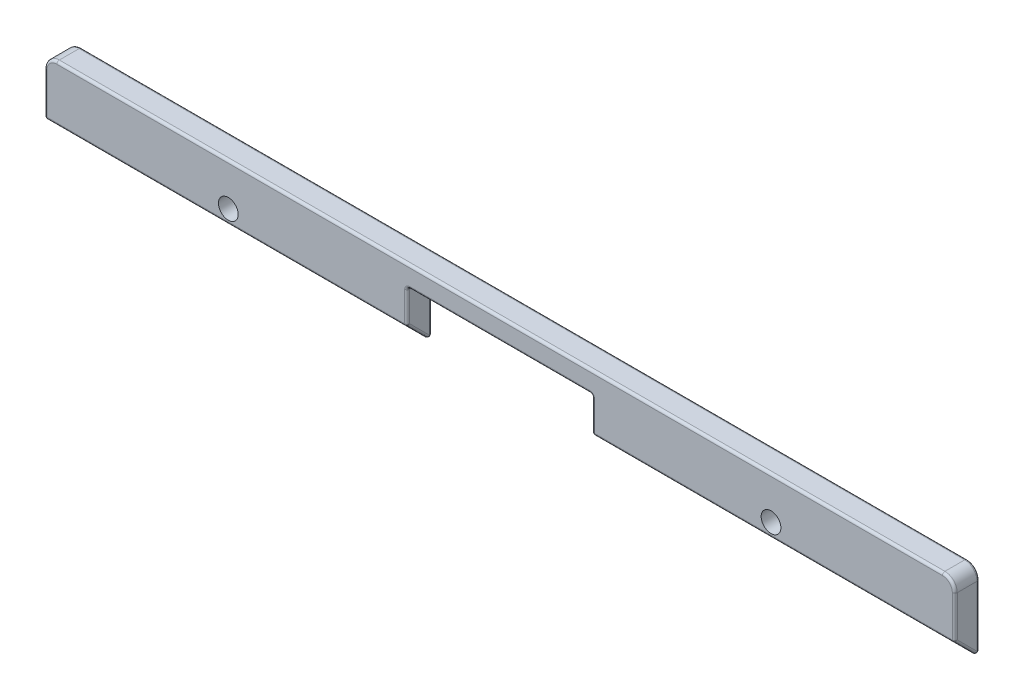
SolidWorks part; units mm, degrees
material "6061-T6 (SS)"
ref_plane "Front Plane" through (0, 0, 0) normal (0, 0, 1) x (1, 0, 0)
ref_plane "Top Plane" through (0, 0, 0) normal (0, 1, 0) x (1, 0, 0)
ref_plane "Right Plane" through (0, 0, 0) normal (1, 0, 0) x (0, 0, -1)
sketch "Sketch1" plane through (0, 0, 0) normal (1, 0, 0) x (0, 0, -1)
  line L0 (-3.0983, 0) -> (1.226, 0) construction
  line L1 (0, -3.2) -> (-2, -1.2)
  line L2 (0, -3.2) -> (0, 3.2)
  line L4 (-2, -1.2) -> (-2, 3.2)
  line L5 (-2, 3.2) -> (0, 3.2)
  dimension "D1" = 2
  dimension "D2" = 45
  dimension "D3" = 6.4
extrude "Boss-Extrude1" add sketch "Sketch1" along normal mid plane 73.8
fillet "Fillet1" radius 0.2 10 edges at (0, 3.2, 0) (0, 3.2, 2) (0, -3.2, 0) (0, -1.2, 2) (36.9, 1, 2) (36.9, 0, 0) (36.9, -2.2, 1) (-36.9, 1, 2) (-36.9, -2.2, 1) (-36.9, 0, 0)
sketch "Sketch4" plane through (0, 0, 0) normal (0, 0, 1) x (1, 0, 0)
  line L1 (7.5, 1.5) -> (-7.5, 1.5)
  line L2 (7.5, 1.5) -> (7.5, -3.2)
  line L3 (7.5, -3.2) -> (-7.5, -3.2)
  line L4 (-7.5, 1.5) -> (-7.5, -3.2)
  line L5 (0, 7.7759) -> (0, -8.8374) construction
  line L8 (-7.5, -3.2) -> (-7.5, 0.8) construction
  dimension "D1" = 4.7
hole_wizard "M2x0.4 Tapped Hole1" positions "Sketch2" profile "Sketch3" tap size "M2x0.4" standard "ANSI Metric" end condition through all
sketch "Sketch2" plane through (0, 0, 2) normal (0, 0, 1) x (1, 0, 0)
  circle A0 centre (-22, -0.2) radius 1.2
  circle A1 centre (-22, -0.2) radius 1.2 construction
  circle A2 centre (22, -0.2) radius 1.2
  circle A3 centre (22, -0.2) radius 1.2 construction
  point P0 (22, -0.2)
  point P2 (0, -0.2)
  point P5 (-22, -0.2)
sketch "Sketch3" plane through (22, -0.2, 2) normal (1, 0, 0) x (0, -1, 0)
  line L0 (0, 0) -> (0, 2)
  line L1 (0, 2) -> (0.8, 2)
  line L2 (0.8, 2) -> (0.8, 0)
  line L5 (0.8, 0) -> (0, 0)
  line L11 (0, -6.35) -> (0, 107.95) construction
  dimension "Thru Tap Drill Dia." = 1.6
  dimension "Thru Tap Drill Depth" = 2
cosmetic thread "Hole Thread1" parameters "D2"=2
cosmetic thread "Hole Thread2" parameters "D2"=2
cosmetic thread "Hole Thread3" parameters "D2"=2
extrude "Cut-Extrude4" cut sketch "Sketch4" along normal through all
fillet "Fillet2" radius 0.2 14 edges at (-7.5, -0.6086, 0) (-7.5, 0.1914, 2) (7.5, 0.1914, 2) (7.5, -0.6086, 0) (-7.5, -1.1937, 1.9848) (-7.5, -2.0586, 1.1414) (7.5, -1.1937, 1.9848) (7.5, -2.0586, 1.1414) (0, 1.5, 0) (0, 1.5, 2) (-7.5, 1.5, 1) (-7.5, -2.9019, 0.1235) (7.5, -2.9019, 0.1235) (7.5, 1.5, 1)
fillet "Fillet3" radius 1 6 edges at (36.8414, 3.1414, 1.9414) (36.8414, 3.1414, 0.0586) (-36.8414, 3.1414, 1.9414) (-36.8414, 3.1414, 0.0586) (-36.9, 3.2, 1) (36.9, 3.2, 1)
